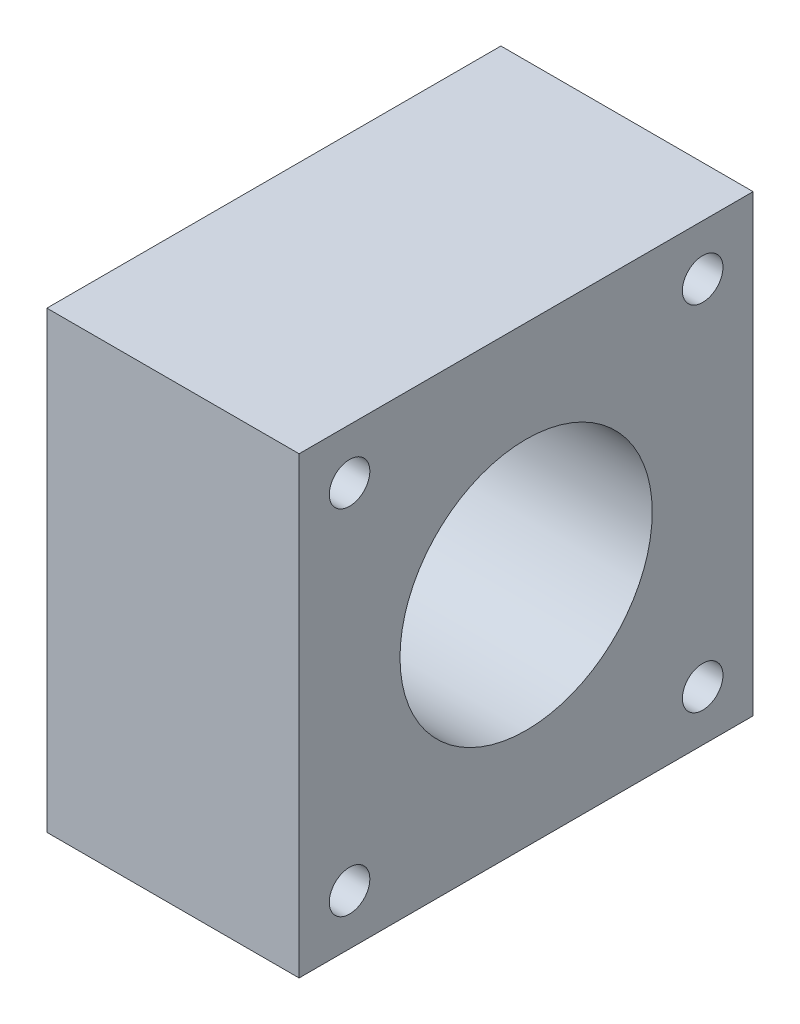
SolidWorks part; units mm, degrees
material "6061 Alloy"
ref_plane "Front Plane" through (0, 0, 0) normal (0, 0, 1) x (1, 0, 0)
ref_plane "Top Plane" through (0, 0, 0) normal (0, 1, 0) x (1, 0, 0)
ref_plane "Right Plane" through (0, 0, 0) normal (1, 0, 0) x (0, 0, -1)
sketch "Sketch2" plane through (0, 0, 0) normal (1, 0, 0) x (0, 0, -1)
  line L1 (0, 0) -> (57.15, 0)
  line L2 (0, 0) -> (0, 57.15)
  line L3 (0, 57.15) -> (57.15, 57.15)
  line L4 (57.15, 0) -> (57.15, 57.15)
  dimension "D1" = 57.15
extrude "Boss-Extrude2" add sketch "Sketch2" along normal blind 31.75
sketch "Sketch3" plane through (31.75, 0, 0) normal (1, 0, 0) x (0, 0, -1)
  line L0 (0, 57.15) -> (57.15, 0) construction
  circle A0 centre (28.575, 28.575) radius 15.875
  dimension "D1" = 31.75
extrude "Cut-Extrude1" cut sketch "Sketch3" against normal through all
sketch "Sketch4" plane through (0, 0, 0) normal (-1, 0, 0) x (0, 0, 1)
  line L0 (-28.575, 46.0375) -> (-28.575, 11.1125) construction
  line L1 (-36.1884, 46.0375) -> (-20.9616, 46.0375)
  line L2 (-20.9616, 11.1125) -> (-36.1884, 11.1125)
  circle A0 centre (-28.575, 28.575) radius 15.875 construction
  arc A1 (-36.1884, 46.0375) -> (-36.1884, 11.1125) centre (-28.575, 28.575) ccw
  arc A2 (-20.9616, 46.0375) -> (-20.9616, 11.1125) centre (-28.575, 28.575) cw
  point P2 (-28.575, 28.575)
  dimension "D2" = 19.05
  dimension "D1" = 34.925
extrude "Cut-Extrude2" cut sketch "Sketch4" against normal blind 2.54
fillet "Fillet1" radius 3.175 4 edges at (1.27, 11.1125, -36.1884) (1.27, 11.1125, -20.9616) (1.27, 46.0375, -20.9616) (1.27, 46.0375, -36.1884)
hole_wizard "1/4-20 Tapped Hole1" positions "Sketch6" profile "Sketch5" tap size "1/4-20" standard "ANSI Inch" end condition through all
sketch "Sketch6" plane through (31.75, 0, 0) normal (1, 0, 0) x (0, 0, -1)
  line L0 (6.35, 50.8) -> (50.8, 6.35) construction
  line L3 (50.8, 50.8) -> (6.35, 6.35) construction
  circle A0 centre (28.575, 28.575) radius 15.875 construction
  point P0 (6.35, 50.8)
  point P2 (50.8, 50.8)
  point P4 (50.8, 6.35)
  point P6 (6.35, 6.35)
  point P18 (28.575, 28.575)
  dimension "D1" = 44.45
sketch "Sketch5" plane through (31.75, 50.8, -6.35) normal (0, 1, 0) x (0, 0, -1)
  line L0 (0, 0) -> (0, 31.75)
  line L1 (0, 31.75) -> (2.5527, 31.75)
  line L2 (2.5527, 31.75) -> (2.5527, 0)
  line L5 (2.5527, 0) -> (0, 0)
  line L11 (0, -6.35) -> (0, 107.95) construction
  dimension "Thread Major Dia." = 5.1054
  dimension "Thru Tap Drill Depth" = 31.75
